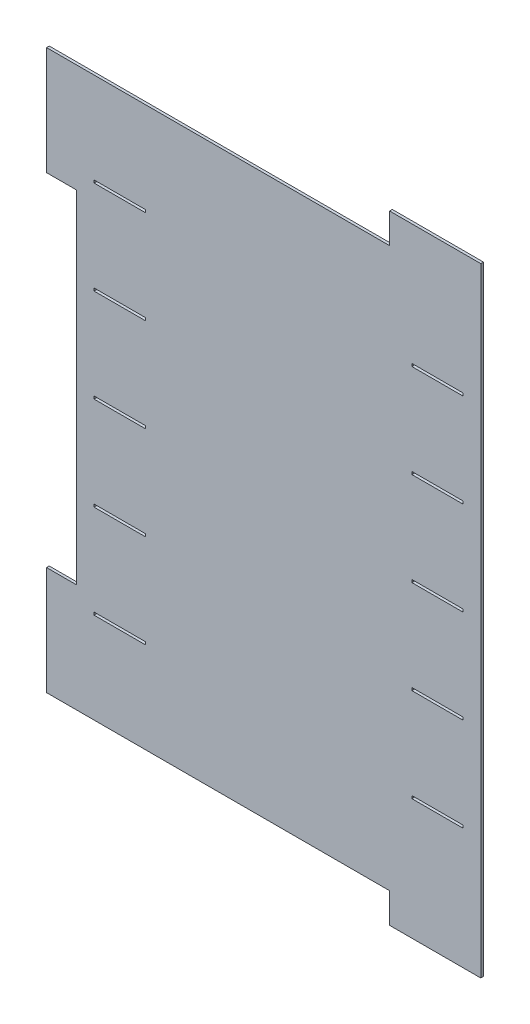
SolidWorks part; units mm, degrees
material "6061-T6 (SS)"
ref_plane "X-Y Datum" through (0, 0, 0) normal (0, 0, 1) x (1, 0, 0)
ref_plane "X-Z Datum" through (0, 0, 0) normal (0, 1, 0) x (1, 0, 0)
ref_plane "Y-Z Datum" through (0, 0, 0) normal (1, 0, 0) x (0, 0, -1)
sketch "Sketch1" plane through (0, 0, 0) normal (0, 0, 1) x (1, 0, 0)
  line L1 (-237.7745, 328.6176) -> (237.7745, 328.6176)
  line L2 (-237.7745, 328.6176) -> (-237.7745, -328.6176)
  line L3 (-237.7745, -328.6176) -> (237.7745, -328.6176)
  line L4 (237.7745, 328.6176) -> (237.7745, -328.6176)
  line L5 (-237.7745, 328.6176) -> (237.7745, -328.6176) construction
  line L6 (-237.7745, -328.6176) -> (237.7745, 328.6176) construction
  point P0 (0, 0)
  dimension "D1" = 475.549
  dimension "D2" = 657.2352
base flange "Base-Flange1" sketch "Sketch1" thickness 3.175 reverse thickness direction no parameters "D1"=1
sketch "Sketch2" plane through (0, 0, 0) normal (0, 0, 1) x (1, 0, 0)
  line L1 (-286.6493, 0) -> (322.8097, 0) construction
  line L2 (-237.7745, 328.6176) -> (-237.7745, -328.6176) construction
  line L3 (-237.7745, 210.6134) -> (237.7745, 210.6134) construction
  line L4 (-217.137, 221.7242) -> (-217.137, 218.5492)
  line L5 (-217.137, 218.5492) -> (-156.812, 218.5492)
  line L11 (0, -43.0151) -> (0, 43.0151) construction
  line L40 (-186.9745, 328.6176) -> (-186.9745, 325.4426) construction
  line L74 (-156.812, 218.5492) -> (-156.812, 221.7242)
  line L75 (0, 328.6176) -> (0, 210.6134) construction
  line L76 (-156.812, 221.7242) -> (-217.137, 221.7242)
  line L77 (237.7745, 328.6176) -> (-237.7745, 328.6176) construction
  line L78 (237.7745, -328.6176) -> (237.7745, 328.6176) construction
  line L79 (-186.9745, 221.7242) -> (-186.9745, 224.8992) construction
  line L80 (217.137, -218.5492) -> (156.812, -218.5492)
  line L85 (217.137, -221.7242) -> (217.137, -218.5492)
  line L90 (156.812, -221.7242) -> (217.137, -221.7242)
  line L94 (156.812, 218.5492) -> (156.812, 221.7242)
  line L95 (217.137, 221.7242) -> (217.137, 218.5492)
  line L96 (217.137, 218.5492) -> (156.812, 218.5492)
  line L97 (156.812, 221.7242) -> (217.137, 221.7242)
  line L123 (-186.9745, 224.8992) -> (-186.9745, 325.4426) construction
  line L124 (156.812, -218.5492) -> (156.812, -221.7242)
  line L125 (-156.812, -218.5492) -> (-156.812, -221.7242)
  line L126 (-217.137, -218.5492) -> (-156.812, -218.5492)
  line L127 (-217.137, -221.7242) -> (-217.137, -218.5492)
  line L128 (-156.812, -221.7242) -> (-217.137, -221.7242)
  line L130 (-217.137, -1.5875) -> (-156.812, -1.5875)
  line L131 (-217.137, -1.5875) -> (-217.137, 1.5875)
  line L132 (-217.137, 1.5875) -> (-156.812, 1.5875)
  line L133 (-156.812, -1.5875) -> (-156.812, 1.5875)
  line L134 (-217.137, -1.5875) -> (-156.812, 1.5875) construction
  line L135 (-217.137, 1.5875) -> (-156.812, -1.5875) construction
  line L136 (-186.9745, 218.5492) -> (-186.9745, 1.5875) construction
  line L137 (-186.9745, -218.5492) -> (-186.9745, -1.5875) construction
  line L138 (217.137, -108.4809) -> (156.812, -108.4809)
  line L139 (-217.137, -111.6559) -> (-156.812, -111.6559)
  line L140 (-217.137, -111.6559) -> (-217.137, -108.4809)
  line L141 (-217.137, -108.4809) -> (-156.812, -108.4809)
  line L142 (-156.812, -111.6559) -> (-156.812, -108.4809)
  line L143 (-217.137, -111.6559) -> (-156.812, -108.4809) construction
  line L144 (-217.137, -108.4809) -> (-156.812, -111.6559) construction
  line L145 (-217.137, 108.4809) -> (-156.812, 108.4809)
  line L146 (-217.137, 108.4809) -> (-217.137, 111.6559)
  line L147 (-217.137, 111.6559) -> (-156.812, 111.6559)
  line L148 (-156.812, 108.4809) -> (-156.812, 111.6559)
  line L149 (-217.137, 108.4809) -> (-156.812, 111.6559) construction
  line L150 (-217.137, 111.6559) -> (-156.812, 108.4809) construction
  line L151 (156.812, -111.6559) -> (156.812, -108.4809)
  line L152 (217.137, -111.6559) -> (156.812, -111.6559)
  line L153 (217.137, -111.6559) -> (217.137, -108.4809)
  line L154 (217.137, 1.5875) -> (156.812, 1.5875)
  line L155 (156.812, -1.5875) -> (156.812, 1.5875)
  line L156 (217.137, -1.5875) -> (156.812, -1.5875)
  line L157 (217.137, -1.5875) -> (217.137, 1.5875)
  line L158 (217.137, 111.6559) -> (156.812, 111.6559)
  line L159 (156.812, 108.4809) -> (156.812, 111.6559)
  line L160 (217.137, 108.4809) -> (156.812, 108.4809)
  line L161 (217.137, 108.4809) -> (217.137, 111.6559)
  line L162 (-186.9745, 111.6559) -> (-186.9745, 218.5492) construction
  line L163 (-156.812, 221.7242) -> (-156.812, 328.6176) construction
  point P25 (-186.9745, 0)
  point P30 (-186.9745, 218.5492)
  point P42 (-186.9745, -110.0684)
  point P47 (-186.9745, 110.0684)
  dimension "D1" = 3.175
  dimension "D3" = 3.175
  dimension "D4" = 3.175
  dimension "D5" = 3.175
  dimension "D7" = 3.175
  dimension "D8" = 60.325
  dimension "D9" = 50.8
  dimension "D2" = 3.175
  dimension "D6" = 100.5434
extrude "Cut-Extrude1" cut sketch "Sketch2" against normal through all both and the other way through all normal cut yes
sketch "Sketch3" plane through (0, 0, 0) normal (0, 0, 1) x (1, 0, 0)
  line L1 (237.7745, 328.6176) -> (130.4874, 328.6176)
  line L2 (237.7745, 328.6176) -> (237.7745, 363.9236)
  line L3 (237.7745, 363.9236) -> (130.4874, 363.9236)
  line L4 (130.4874, 328.6176) -> (130.4874, 363.9236)
  line L5 (-237.7745, 328.6176) -> (-273.0805, 328.6176)
  line L6 (-237.7745, 328.6176) -> (-237.7745, 201.1451)
  line L7 (-237.7745, 201.1451) -> (-273.0805, 201.1451)
  line L8 (-273.0805, 328.6176) -> (-273.0805, 201.1451)
  line L9 (-237.7745, -328.6176) -> (-273.0805, -328.6176)
  line L10 (-237.7745, -328.6176) -> (-237.7745, -201.1451)
  line L11 (-237.7745, -201.1451) -> (-273.0805, -201.1451)
  line L12 (-273.0805, -328.6176) -> (-273.0805, -201.1451)
  line L13 (237.7745, -328.6176) -> (130.4874, -328.6176)
  line L14 (237.7745, -328.6176) -> (237.7745, -363.9236)
  line L15 (237.7745, -363.9236) -> (130.4874, -363.9236)
  line L16 (130.4874, -328.6176) -> (130.4874, -363.9236)
extrude "Boss-Extrude1" add sketch "Sketch3" against normal up to surface (3.175 mm away) up to face at (186.9745, 0, -3.175)
sketch "Bend-Lines1" [suppressed] plane through (0, 0, 0) normal (0, 1, 0) x (1, 0, 0)
sketch "Bounding-Box1" [suppressed] plane through (0, 0, 0) normal (0, 1, 0) x (1, 0, 0)
sheet metal parameters "Sheet-Metal1" thickness 3.175 parameters "D1"=1
flat pattern "Flat-Pattern1" [suppressed]
sketch "Bend-Lines2" plane through (0, 0, 0) normal (0, 1, 0) x (1, 0, 0)
sketch3d "Bounding-Box2" [suppressed]
  line L0 (232.0925, 287.655, 0) -> (232.0925, -287.655, 0) construction
  line L1 (-232.0925, 287.655, 0) -> (-232.0925, -287.655, 0) construction
  line L2 (232.0925, 287.655, 0) -> (-232.0925, 287.655, 0) construction
  line L3 (232.0925, -287.655, 0) -> (-232.0925, -287.655, 0) construction
sheet metal parameters "Sheet-Metal2" thickness 3.175 parameters "D1"=1
flat pattern "Flat-Pattern1"
sketch "Bend-Lines2" plane through (0, 0, 0) normal (0, 1, 0) x (1, 0, 0)
sketch3d "Bounding-Box2" [suppressed]
  line L0 (236.6874, 307.3451, 0) -> (236.6874, -307.3451, 0) construction
  line L1 (-236.6874, 307.3451, 0) -> (-236.6874, -307.3451, 0) construction
  line L2 (236.6874, 307.3451, 0) -> (-236.6874, 307.3451, 0) construction
  line L3 (236.6874, -307.3451, 0) -> (-236.6874, -307.3451, 0) construction
sheet metal parameters "Sheet-Metal3" thickness 3.175 parameters "D1"=1
flat pattern "Flat-Pattern1"
sketch "Bend-Lines2" plane through (0, 0, 0) normal (0, 1, 0) x (1, 0, 0)
sketch3d "Bounding-Box2" [suppressed]
  line L0 (237.7745, 363.9236, 0) -> (237.7745, -363.9236, 0) construction
  line L1 (-273.0805, 363.9236, 0) -> (-273.0805, -363.9236, 0) construction
  line L2 (237.7745, 363.9236, 0) -> (-273.0805, 363.9236, 0) construction
  line L3 (237.7745, -363.9236, 0) -> (-273.0805, -363.9236, 0) construction
